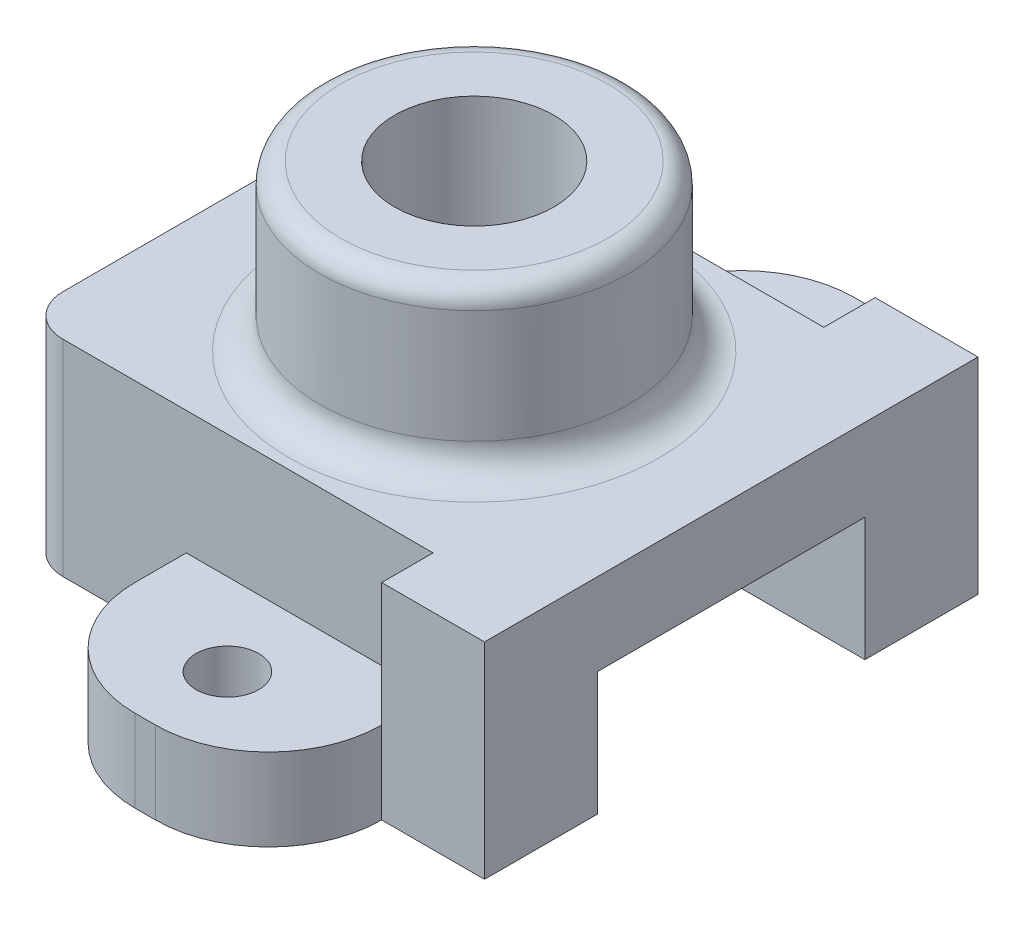
SolidWorks part; units mm, degrees
ref_plane "Front Plane" through (0, 0, 0) normal (0, 0, 1) x (1, 0, 0)
ref_plane "Top Plane" through (0, 0, 0) normal (0, 1, 0) x (1, 0, 0)
ref_plane "Right Plane" through (0, 0, 0) normal (1, 0, 0) x (0, 0, -1)
sketch "Sketch1" plane through (0, 0, 0) normal (0, 1, 0) x (1, 0, 0)
  line L0 (-1, -3) -> (23, -3)
  line L1 (0, 0) -> (22, 0)
  line L2 (0, 0) -> (0, 13)
  line L3 (0, 13) -> (22, 13)
  line L4 (22, 0) -> (22, 13)
  line L5 (25, -1) -> (25, 14)
  line L6 (-1, 16) -> (23, 16)
  line L7 (-3, -1) -> (-3, 14)
  line L8 (-3, -3) -> (25, -3) construction
  line L9 (25, -3) -> (25, 16) construction
  line L10 (-3, 16) -> (25, 16) construction
  line L11 (-3, -3) -> (-3, 16) construction
  line L12 (25, 14) -> (25, 16)
  line L13 (25, 16) -> (23, 16)
  line L14 (25, -1) -> (25, -3)
  line L15 (25, -3) -> (23, -3)
  arc A2 (-1, 16) -> (-3, 14) centre (-1, 14) ccw
  arc A3 (-1, -3) -> (-3, -1) centre (-1, -1) cw
  dimension "D1" = 22
  dimension "D2" = 13
  dimension "D3" = 3
extrude "Boss-Extrude1" add sketch "Sketch1" along normal blind 6
sketch "Sketch2" plane through (0, 6, 0) normal (0, 1, 0) x (1, 0, 0)
  line L0 (25, 14) -> (25, -1)
  line L1 (23, -3) -> (-1, -3)
  line L2 (-3, -1) -> (-3, 14)
  line L3 (-1, 16) -> (23, 16)
  line L4 (25, 16) -> (-1, 16) construction
  line L5 (23, 16) -> (25, 16)
  line L6 (25, -3) -> (25, 16) construction
  line L7 (25, 16) -> (25, 14)
  line L8 (25, -1) -> (25, -3)
  line L9 (-1, -3) -> (25, -3) construction
  line L10 (25, -3) -> (23, -3)
  arc A1 (-1, -3) -> (-3, -1) centre (-1, -1) cw
  arc A2 (-3, 14) -> (-1, 16) centre (-1, 14) cw
extrude "Boss-Extrude2" add sketch "Sketch2" along normal blind 2
sketch "Sketch3" plane through (0, 0, 0) normal (0, -1, 0) x (1, 0, 0)
  line L0 (-1, 3) -> (25, 3) construction
  line L1 (5, 3) -> (17, 3)
  line L2 (5, 3) -> (5, 5.5)
  line L3 (10.5, 11) -> (11.5, 11)
  line L4 (17, 3) -> (17, 5.5)
  line L5 (25, -16) -> (-1, -16) construction
  line L6 (17, -16) -> (5, -16)
  line L7 (17, -16) -> (17, -18.5)
  line L8 (11.5, -24) -> (10.5, -24)
  line L9 (5, -16) -> (5, -18.5)
  line L10 (25, 3) -> (25, -16) construction
  line L11 (-3, -14) -> (-3, 1) construction
  arc A0 (17, -18.5) -> (11.5, -24) centre (11.5, -18.5) cw
  arc A1 (10.5, -24) -> (5, -18.5) centre (10.5, -18.5) cw
  arc A2 (5, 5.5) -> (10.5, 11) centre (10.5, 5.5) cw
  arc A3 (11.5, 11) -> (17, 5.5) centre (11.5, 5.5) cw
  point P16 (17, -17.25)
  point P19 (17, -24)
  point P26 (17, 11)
  dimension "D7" = 5.5
  dimension "D1" = 8
  dimension "D2" = 8
  dimension "D3" = 8
  dimension "D4" = 8
  dimension "D5" = 8
  dimension "D6" = 8
extrude "Boss-Extrude3" add sketch "Sketch3" against normal up to surface (8 mm away) up to face at (6.8619, 8, -6.5)
sketch "Sketch4" plane through (0, 0, 0) normal (0, -1, 0) x (-1, 0, 0)
  line L0 (-17, 18.5) -> (-17, 16) construction
  line L2 (-10.5, 24) -> (-11.5, 24) construction
  line L3 (-11.5, -11) -> (-10.5, -11) construction
  line L4 (-5, -5.5) -> (-5, -3) construction
  circle A0 centre (-11, 20) radius 1.525
  circle A1 centre (-11, -7) radius 1.524
  point P9 (-11, 24)
  dimension "D1" = 3.048
  dimension "D2" = 3.05
  dimension "D3" = 6
  dimension "D4" = 4
  dimension "D5" = 4
  dimension "D6" = 6
extrude "Cut-Extrude1" cut sketch "Sketch4" against normal through all
sketch "Sketch5" plane through (25, 0, 0) normal (1, 0, 0) x (0, 0, -1)
  line L0 (-3, 0) -> (16, 0) construction
  line L1 (11, 0) -> (2, 0)
  line L2 (11, 0) -> (11, 4.0887)
  line L3 (11, 4.0887) -> (2, 4.0887)
  line L4 (2, 0) -> (2, 4.0887)
  line L5 (16, 8) -> (16, 0) construction
  line L6 (-3, 8) -> (-3, 0) construction
  dimension "D1" = 5
  dimension "D2" = 5
extrude "Cut-Extrude2" cut sketch "Sketch5" against normal through all
fillet "Fillet1" radius 2 4 edges at (-1.5, 4.0887, -2) (-1.5, 4.0887, -11) (23.5, 4.0887, -11) (23.5, 4.0887, -2)
sketch "Sketch6" plane through (0, 8, 0) normal (0, 1, 0) x (1, 0, 0)
  line L0 (-1, -3) -> (5, -3) construction
  line L1 (17, 16) -> (5, 16)
  line L2 (17, 16) -> (17, 29.009)
  line L3 (17, 29.009) -> (5, 29.009)
  line L4 (5, 16) -> (5, 29.009)
  line L5 (19.0682, -16.009) -> (3.2299, -16.009)
  line L6 (19.0682, -16.009) -> (19.0682, -3)
  line L7 (19.0682, -3) -> (3.2299, -3)
  line L8 (3.2299, -16.009) -> (3.2299, -3)
extrude "Cut-Extrude3" cut sketch "Sketch6" against normal blind 4
sketch "Sketch7" plane through (25, 0, 0) normal (1, 0, 0) x (0, 0, -1)
  line L0 (18.5, 4) -> (18.5, 0) construction
  line L1 (16, 8) -> (18.5, 8)
  line L2 (16, 8) -> (16, 0)
  line L3 (16, 0) -> (18.5, 0)
  line L4 (18.5, 8) -> (18.5, 0)
  line L5 (-3, 8) -> (-5.5, 8)
  line L6 (-3, 8) -> (-3, 0)
  line L7 (-3, 0) -> (-5.5, 0)
  line L8 (-5.5, 8) -> (-5.5, 0)
  line L9 (18.5, 0) -> (16, 0) construction
  line L10 (-5.5, 4) -> (-5.5, 0) construction
  line L11 (-3, 0) -> (-5.5, 0) construction
extrude "Boss-Extrude5" add sketch "Sketch7" against normal blind 3
fillet "Fillet3" radius 2.5 1 edges at (22, 4, -16)
fillet "Fillet4" radius 2.5 1 edges at (22, 4, 3)
sketch "Sketch9" plane through (25, 0, 0) normal (1, 0, 0) x (0, 0, -1)
  line L1 (18.5, 8) -> (-5.5, 8)
  line L2 (18.5, 8) -> (18.5, 0)
  line L3 (18.5, 0) -> (-5.5, 0)
  line L4 (-5.5, 8) -> (-5.5, 0)
extrude "Cut-Extrude5" cut sketch "Sketch9" against normal blind 3
sketch "Sketch10" plane through (0, 8, 0) normal (0, 1, 0) x (1, 0, 0)
  line L1 (17, 16) -> (22, 16)
  line L2 (17, 16) -> (17, 18.5)
  line L3 (17, 18.5) -> (22, 18.5)
  line L4 (22, 16) -> (22, 18.5)
  line L5 (17, -3) -> (22, -3)
  line L6 (17, -3) -> (17, -5.5)
  line L7 (17, -5.5) -> (22, -5.5)
  line L8 (22, -3) -> (22, -5.5)
extrude "Boss-Extrude6" add sketch "Sketch10" against normal up to surface (8 mm away) up to face at (8.7574, 0, 3.5482)
sketch "Sketch11" plane through (0, 8, 0) normal (0, 1, 0) x (1, 0, 0)
  line L0 (17, -3) -> (-1, -3)
  line L1 (-3, -1) -> (-3, 14)
  line L2 (-1, 16) -> (17, 16)
  line L3 (17, 16) -> (17, 18.5)
  line L4 (17, 18.5) -> (22, 18.5)
  line L5 (22, 18.5) -> (22, -5.5)
  line L6 (22, -5.5) -> (17, -5.5)
  line L7 (17, -5.5) -> (17, -3)
  arc A0 (-3, -1) -> (-1, -3) centre (-1, -1) ccw construction
  arc A1 (-1, -3) -> (-3, -1) centre (-1, -1) cw
  arc A2 (-3, 14) -> (-1, 16) centre (-1, 14) cw
extrude "Boss-Extrude7" add sketch "Sketch11" along normal blind 2
sketch "Sketch12" plane through (0, 10, 0) normal (0, 1, 0) x (1, 0, 0)
  line L0 (22, -5.5) -> (22, 18.5) construction
  line L2 (-1, -3) -> (17, -3) construction
  circle A0 centre (9.5, 6.5) radius 7.5
  point P2 (0, 0)
  dimension "D1" = 12.5
  dimension "D3" = 15
  dimension "D2" = 9.5
extrude "Boss-Extrude8" add sketch "Sketch12" along normal blind 8
sketch "Sketch13" plane through (0, 18, 0) normal (0, 1, 0) x (1, 0, 0)
  circle A0 centre (9.5, 6.5) radius 3.8735
extrude "Cut-Extrude6" cut sketch "Sketch13" against normal up to surface (8 mm away) up to face at (9.5, 10, -14)
fillet "Fillet5" radius 1.5 1 edges at (9.5, 10, -14)
fillet "Fillet7" radius 1 1 edges at (9.5, 18, 1)
